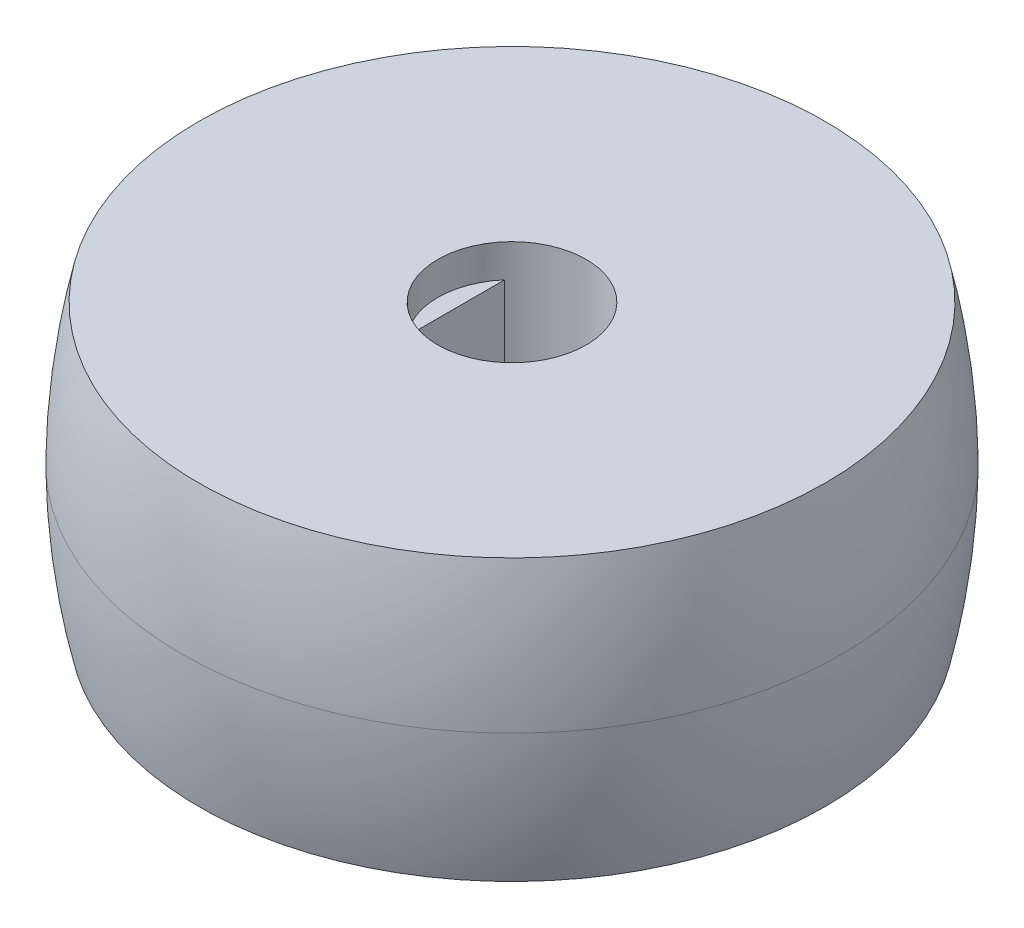
SolidWorks part; units mm, degrees
ref_plane "Front Plane" through (0, 0, 0) normal (0, 0, 1) x (1, 0, 0)
ref_plane "Top Plane" through (0, 0, 0) normal (0, 1, 0) x (1, 0, 0)
ref_plane "Right Plane" through (0, 0, 0) normal (1, 0, 0) x (0, 0, -1)
sketch "Sketch1" plane through (0, 0, 0) normal (0, 0, 1) x (1, 0, 0)
  line L0 (0, 0) -> (0, -8.5) construction
  line L1 (0, -8.5) -> (19, -8.5)
  line L2 (0, 0) -> (20, 0)
  line L5 (0, 0) -> (0, -8.5)
  line L6 (0, -8.5) -> (0, -17.4069) construction
  arc A0 (20, 0) -> (19, -8.5) centre (-19.998, 0.3968) cw
  dimension "D2" = 40
  dimension "D1" = 1
  dimension "D3" = 20
  dimension "D4" = 8.5
revolve "Revolve1" add sketch "Sketch1" angle 360 about L0
mirror "Mirror1" about plane through (0, 0, 0) normal (0, 1, 0) of "Revolve1"
sketch "Sketch2" plane through (0, 8.5, 0) normal (0, 1, 0) x (1, 0, 0)
  line L0 (3.4, -2.9479) -> (3.4, 2.9479)
  line L1 (-3.4, -2.9479) -> (-3.4, 2.9479)
  line L2 (0, 0) -> (0, -2.1539) construction
  circle A0 centre (0, 0) radius 4.5
  circle A1 centre (0, 0) radius 1.65
  dimension "D1" = 9
  dimension "D2" = 6.8
  dimension "D3" = 3.3
extrude "Cut-Extrude1" cut sketch "Sketch2" against normal blind 2 contours L0 A0 L1 | A1 | L0 A0 | L1 A0 region at (0, 8.5, 4.3872) region at (3.845, 8.5, 0) region at (-3.845, 8.5, 0) region at (0, 8.5, 0)
extrude "Cut-Extrude2" cut sketch "Sketch2<3>" against normal through all contours A1 region at (0, 8.5, 0)
sketch "Sketch2<3>" plane through (0, 8.5, 0) normal (0, 1, 0) x (1, 0, 0) same geometry as "Sketch2"
extrude "Cut-Extrude3" cut sketch "Sketch2<5>" against normal blind 4.5 from surface contours L0 A0 L1 A1 region at (0, 8.5, 4.3872) starting at face at (0, 6.5, 1.65)
sketch "Sketch2<5>" plane through (0, 8.5, 0) normal (0, 1, 0) x (1, 0, 0) same geometry as "Sketch2"
